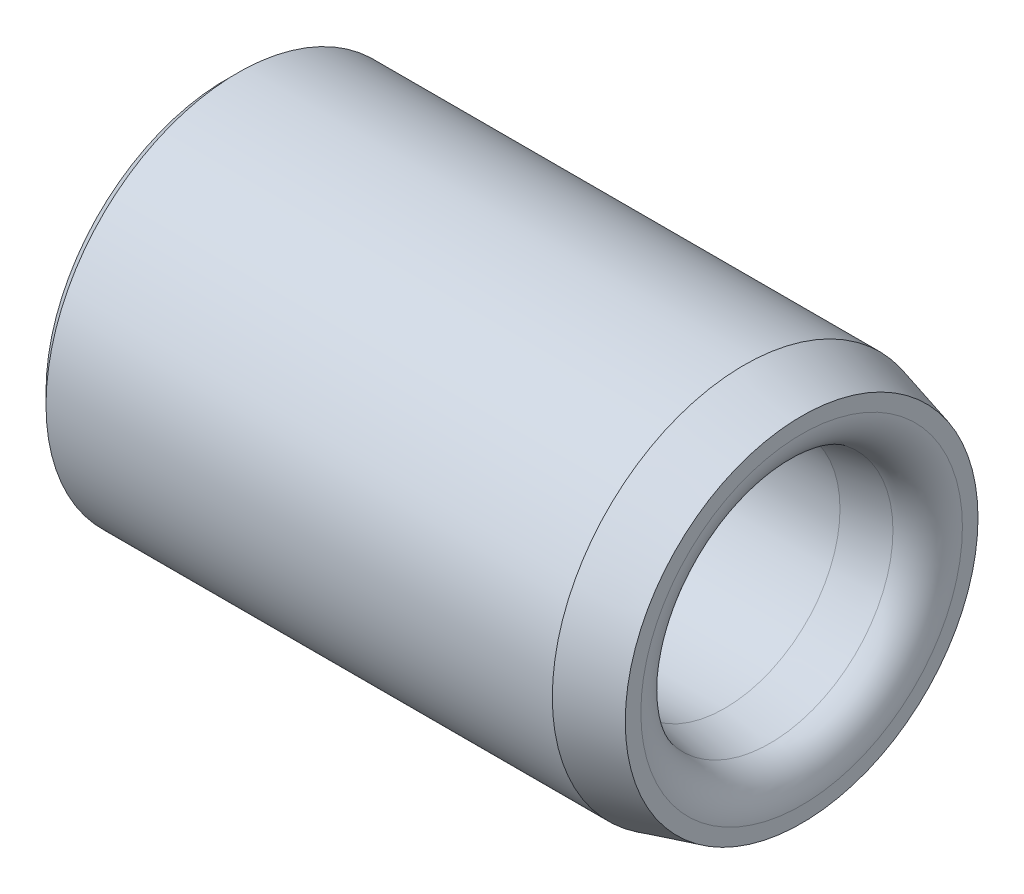
SolidWorks part; units mm, degrees
material "黄銅"
ref_plane "Front Plane" through (0, 0, 0) normal (0, 0, 1) x (1, 0, 0)
ref_plane "Top Plane" through (0, 0, 0) normal (0, 1, 0) x (1, 0, 0)
ref_plane "Right Plane" through (0, 0, 0) normal (1, 0, 0) x (0, 0, -1)
ref_axis "Axis_X" through (0, 0, 0) along (1, 0, 0)
ref_axis "Axis_Y" through (0, 0, 0) along (0, 1, 0)
ref_axis "Axis_Z" through (0, 0, 0) along (0, 0, 1)
sketch "Sketch1" plane through (0, 0, 0) normal (0, 0, 1) x (1, 0, 0)
  line L0 (0, 0) -> (15, 0) construction
  line L1 (0, 3) -> (0, 5)
  line L2 (0, 5) -> (15, 5)
  line L4 (15, 5) -> (15, 3)
  line L6 (15, 3) -> (0, 3)
  dimension "L" = 15
  dimension "D_s" = 6
  dimension "D" = 10
revolve "Revolve1" add sketch "Sketch1" angle 360 about L0
chamfer "Chamfer1" distance 0.3 angle 45 1 edges at (0, 0, 5)
chamfer "Chamfer2" distance 1.5 angle 15 1 edges at (15, 0, 5) first distance on face at (0.3, 0, -5)
chamfer "Chamfer3" distance 2 angle 10 2 edges at (0, 0, 3) (15, 0, 3) first distance on face at (15, 0, 3)
fillet "Fillet1" radius 1 2 edges at (0, 0, -3.3527) (15, 0, 3.3527)
